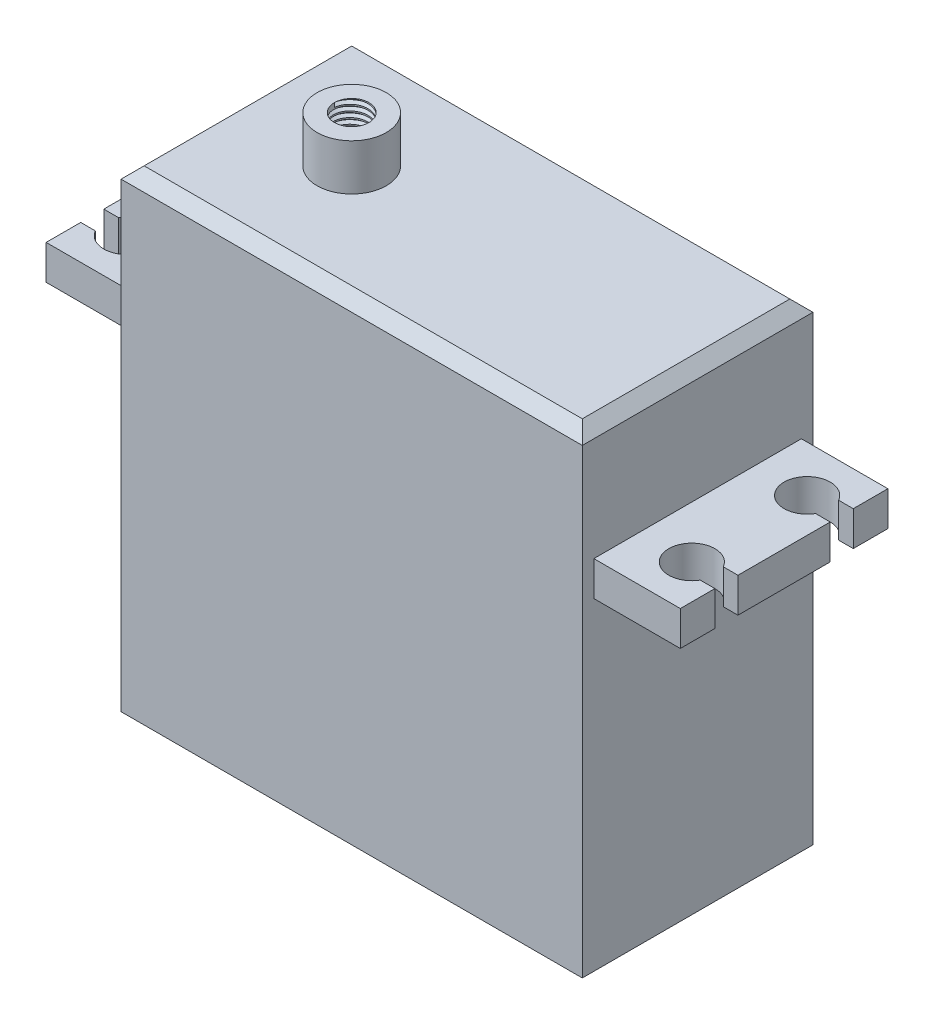
SolidWorks part; units mm, degrees
ref_plane "Front Plane" through (0, 0, 0) normal (0, 0, 1) x (1, 0, 0)
ref_plane "Top Plane" through (0, 0, 0) normal (0, 1, 0) x (1, 0, 0)
ref_plane "Right Plane" through (0, 0, 0) normal (1, 0, 0) x (0, 0, -1)
sketch "Sketch1" plane through (0, 0, 0) normal (0, 1, 0) x (1, 0, 0)
  line L1 (-20, 10) -> (20, 10)
  line L2 (-20, 10) -> (-20, -10)
  line L3 (-20, -10) -> (20, -10)
  line L4 (20, 10) -> (20, -10)
  line L5 (-20, 10) -> (20, -10) construction
  line L6 (-20, -10) -> (20, 10) construction
  point P0 (0, 0)
  dimension "D1" = 40
  dimension "D2" = 20
extrude "Body" add sketch "Sketch1" along normal blind 41
ref_plane "Plane1" through (0, 28, 0) normal (0, 1, 0) x (1, 0, 0)
sketch "Sketch2" plane through (0, 28, 0) normal (0, 1, 0) x (1, 0, 0)
  line L1 (-27.5, 9) -> (27.5, 9)
  line L2 (-27.5, 9) -> (-27.5, -9)
  line L3 (-27.5, -9) -> (27.5, -9)
  line L4 (27.5, 9) -> (27.5, -9)
  line L5 (-27.5, 9) -> (27.5, -9) construction
  line L6 (-27.5, -9) -> (27.5, 9) construction
  point P0 (0, 0)
  dimension "D1" = 18
  dimension "D2" = 55
extrude "Fin" add sketch "Sketch2" along normal blind 3
sketch "Sketch3" plane through (0, 28, 0) normal (0, 1, 0) x (1, 0, 0)
  line L1 (0, -11) -> (0, 11) construction
  line L2 (-27.5, -9) -> (-20, -9) construction
  line L3 (-20, 9) -> (-27.5, 9) construction
  line L4 (-27.5, 9) -> (-27.5, -9) construction
  circle A0 centre (-24.5, 5) radius 2
  circle A1 centre (-24.5, -5) radius 2
  circle A2 centre (24.5, -5) radius 2
  circle A3 centre (24.5, 5) radius 2
  dimension "D1" = 4
  dimension "D2" = 4
  dimension "D3" = 10
  dimension "D4" = 3
  dimension "D5" = 4
  dimension "D6" = 4
extrude "Hole for screws" cut sketch "Sketch3" along normal up to next
ref_plane "Plane2" through (-20, 0, 0) normal (-1, 0, 0) x (0, 0, 1)
sketch "Sketch4" plane through (-20, 0, 0) normal (-1, 0, 0) x (0, 0, 1)
  line L0 (-10, 0) -> (10, 0) construction
  line L1 (-3.5, 7) -> (3.5, 7)
  line L2 (-3.5, 7) -> (-3.5, 3)
  line L3 (-3.5, 3) -> (3.5, 3)
  line L4 (3.5, 7) -> (3.5, 3)
  line L5 (-3.5, 7) -> (3.5, 3) construction
  line L6 (-3.5, 3) -> (3.5, 7) construction
  point P0 (0, 5)
  dimension "D1" = 7
  dimension "D2" = 3
  dimension "D3" = 4
extrude "Wire out" add sketch "Sketch4" along normal blind 0.5
ref_plane "Plane3" through (0, 41, 0) normal (0, 1, 0) x (1, 0, 0)
sketch "Sketch5" plane through (0, 41, 0) normal (0, 1, 0) x (1, 0, 0)
  line L0 (-20, 11) -> (-20, -11) construction
  line L1 (-20, -10) -> (20, -10) construction
  circle A0 centre (-10, 0) radius 10 construction
  circle A1 centre (-10, 0) radius 3
  dimension "D1" = 6
  dimension "D2" = 10
  dimension "D3" = 10
extrude "Axle" add sketch "Sketch5" along normal blind 4
ref_plane "Plane4" through (0, 45, 0) normal (0, 1, 0) x (1, 0, 0)
sketch "Sketch6" plane through (0, 45, 0) normal (0, 1, 0) x (1, 0, 0)
  circle A0 centre (-10, 0) radius 1.5
  dimension "D1" = 3
extrude "Cut-Extrude1" cut sketch "Sketch6" against normal blind 4 contours A0
sketch "Sketch8" plane through (0, 28, 0) normal (0, 1, 0) x (1, 0, 0)
  line L0 (-26, 6) -> (-28, 6)
  line L1 (-28, 6) -> (-28, 4)
  line L2 (-28, 4) -> (-26, 4)
  line L3 (-26, 4) -> (-26, 6)
  line L4 (-20, 9) -> (-27.5, 9) construction
  line L8 (-24.75, 0) -> (24.75, 0) construction
  line L9 (-26, -6) -> (-28, -6)
  line L10 (-26, -4) -> (-26, -6)
  line L11 (-28, -4) -> (-26, -4)
  line L12 (-28, -6) -> (-28, -4)
  line L13 (0, -11) -> (0, 11) construction
  line L14 (28, -6) -> (28, -4)
  line L15 (28, -4) -> (26, -4)
  line L16 (26, -4) -> (26, -6)
  line L17 (26, -6) -> (28, -6)
  line L18 (26, 6) -> (28, 6)
  line L19 (28, 6) -> (28, 4)
  line L20 (28, 4) -> (26, 4)
  line L21 (26, 4) -> (26, 6)
  line L22 (-20, 10) -> (-20, -10) construction
  dimension "D1" = 2
  dimension "D2" = 2
  dimension "D3" = 3
  dimension "D4" = 6
extrude "Cut-Extrude4" cut sketch "Sketch8" along normal up to next
sketch "Sketch9" plane through (0, 45, 0) normal (0, 1, 0) x (1, 0, 0)
  point P0 (-10, 0)
sketch "Sketch10" plane through (0, 0, 0) normal (0, 1, 0) x (1, 0, 0)
  point P0 (-10, 0)
sketch3d "3DSketch1"
  line L0 (-10, 45, 0) -> (-10, -49955, 0) construction
thread "Thread1" pitch 0.5 method cut profile "Thread Profile1" start angle 0, offset 0, length 0, pitch 0.5, diameter 3
ref_plane "Plane5" through (-11.5, 45, 0) normal (0, 0, 1) x (-1, 0, 0)
sketch "Thread Profile1" plane through (-11.5, 45, 0) normal (0, 0, 1) x (-1, 0, 0)
  line L0 (0, 0) -> (0, 0.5) construction
  line L1 (0, 0) -> (0.2706, 0.1562)
  line L2 (0.2706, 0.1562) -> (0.2706, 0.2187)
  line L3 (0.2706, 0.2187) -> (0, 0.375)
  line L4 (0.2706, 0.1875) -> (0, 0.1875) construction
  line L11 (0, 0) -> (0, 0.375)
  point P2 (0, 0)
  dimension "Pitch" = 0.5
  dimension "Profile_Angle" = 60
  dimension "Profile_Land" = 0.0625
  dimension "Profile_Height" = 0.2706
chamfer "Chamfer1" distance 1 angle 45 4 edges at (-20, 41, 0) (0, 41, -10) (20, 41, 0) (0, 41, 10)
